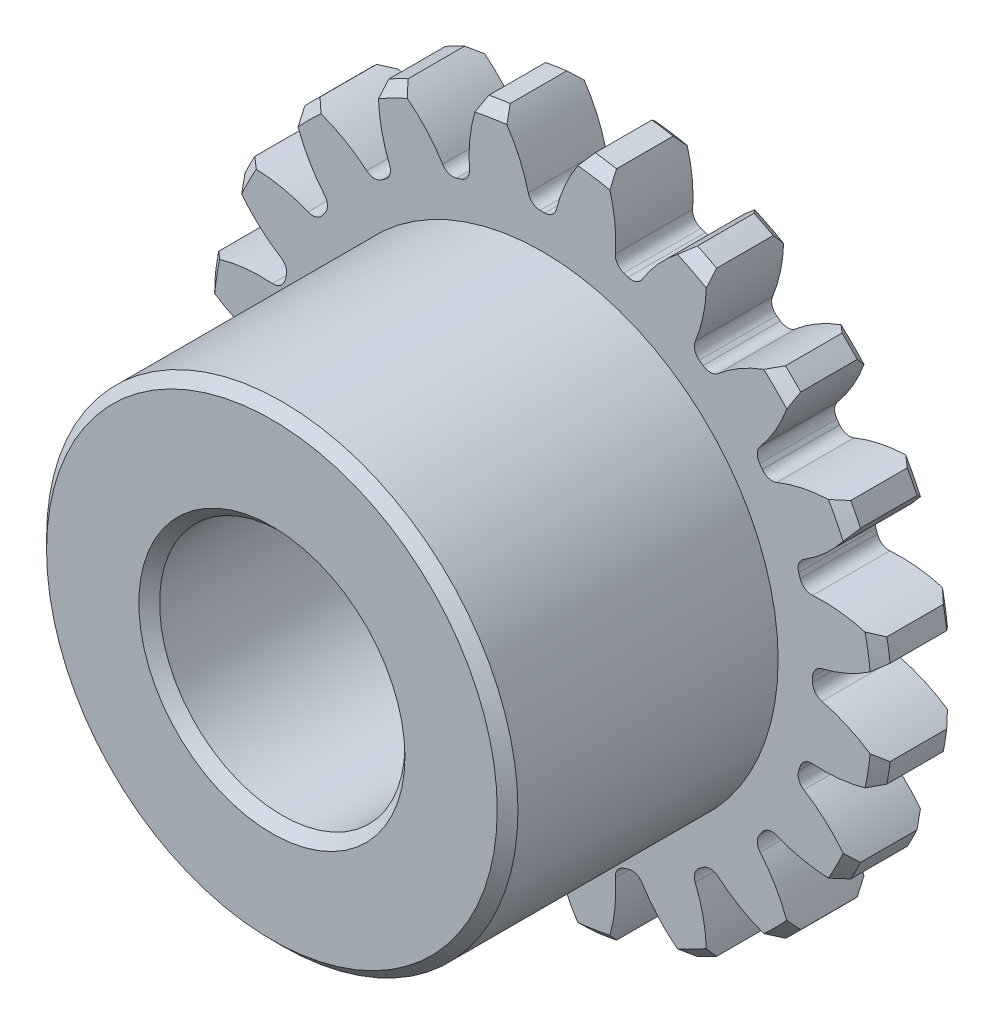
SolidWorks part; units mm, degrees
material "PET"
ref_plane "Front Plane" through (0, 0, 0) normal (0, 0, 1) x (1, 0, 0)
ref_plane "Top Plane" through (0, 0, 0) normal (0, 1, 0) x (1, 0, 0)
ref_plane "Right Plane" through (0, 0, 0) normal (1, 0, 0) x (0, 0, -1)
sketch "Sketch1" plane through (0, 0, 0) normal (0, 0, 1) x (1, 0, 0)
  line L0 (0, 0) -> (0, 8) construction
  line L1 (-2.5712, 8.9358) -> (2.5712, 7.0642) construction
  circle A0 centre (0, 0) radius 7 construction
  circle A1 centre (0, 0) radius 8.8 construction
  circle A2 centre (0, 0) radius 8 construction
  circle A3 centre (0, 0) radius 7.5175 construction
  circle A4 centre (0, 0) radius 6.1 construction
  circle A5 centre (0, 0) radius 3.175 construction
  point P8 (0.4, 0)
  point P13 (10, 0)
  dimension "OD" = 17.6
  dimension "Root Diameter" = 14
  dimension "Gear Pitch Diameter" = 16
  dimension "Base Diameter" = 15.0351
  dimension "Hub Diameter" = 12.2
  dimension "For Shaft Diameter" = 6.35
  dimension "Pressure Angle" = 20
  dimension "Number of Teeth" = 20
  dimension "Module" = 0.8
sketch "Sketch2" plane through (0, 0, 0) normal (1, 0, 0) x (0, 0, -1)
  line L0 (-7, 0) -> (2, 0) construction
  line L1 (2, 8.8) -> (2, -8.8) construction
  line L2 (0, -6.1) -> (-7, -6.1) construction
  line L3 (-7, 8.8) -> (2, 8.8) construction
  line L8 (-7, -6.1) -> (-7, 6.1) construction
  point P4 (0, 8.8)
  point P5 (-3.5, 0)
  dimension "Overall Width" = 9
  dimension "Hub Width" = 7
  dimension "Approx Set Screw Positon" = 3.5
  dimension "Face Width" = 2
sketch "Sketch3" plane through (0, 0, 0) normal (0, 0, 1) x (1, 0, 0)
  circle A0 centre (0, 0) radius 8.8
  circle A1 centre (0, 0) radius 8.8 construction
extrude "Boss-Extrude1" add sketch "Sketch3" against normal up to vertex (2 mm away) and the other way up to vertex (7 mm away) up to point (0, 0, -2) other way up to point (0, 0, 7)
sketch "Sketch5" plane through (0, 0, 0) normal (1, 0, 0) x (0, 0, -1)
  line L1 (0, 6.1) -> (-7, 6.1)
  line L2 (0, 6.1) -> (0, 8.8)
  line L3 (0, 8.8) -> (-7, 8.8)
  line L4 (-7, 6.1) -> (-7, 8.8)
  line L5 (-7, 0) -> (2, 0)
  line L6 (-7, 0) -> (-7, 3.175)
  line L7 (-7, 3.175) -> (2, 3.175)
  line L8 (2, 0) -> (2, 3.175)
  point P5 (0, 6.1)
  point P12 (0, 3.175)
revolve "Cut-Revolve1" cut sketch "Sketch5" angle 360 about L0
sketch "Sketch6" plane through (0, 0, -2) normal (0, 0, 1) x (1, 0, 0)
  line L1 (-6.1, -0.4064) -> (6.1, -0.4064)
  line L2 (-6.1, -0.4064) -> (-6.1, 0.4064)
  line L3 (-6.1, 0.4064) -> (6.1, 0.4064)
  line L4 (6.1, -0.4064) -> (6.1, 0.4064)
  line L5 (0, 0.4064) -> (0, -0.4064) construction
  line L6 (-6.1, 0) -> (6.1, 0) construction
  circle A1 centre (0, 0) radius 6.1 construction
  point P0 (0, 0)
  dimension "D1" = 0.8128
extrude "Cut-Extrude2" cut sketch "Sketch6" along normal blind 1
chamfer "Chamfer1" distance 0.2684 angle 45 6 edges at (8.8, 0, 0) (8.8, 0, -2) (3.175, 0, 7) (6.1, 0, 7) (0, 3.175, -2) (0, -3.175, -2)
sketch "Sketch4" plane through (0, 0, 0) normal (0, 0, 1) x (1, 0, 0)
  line L0 (6.9929, 0.3142) -> (6.9929, -0.3142)
  arc A3 (8.7308, 1.1015) -> (8.7308, -1.1015) centre (0, 0) cw
  circle A4 centre (0, 0) radius 8.8 construction
  arc A5 (6.9929, 0.3142) -> (8.7308, 1.1015) centre (6.2993, 4.157) ccw
  circle A8 centre (0, 0) radius 7 construction
  arc A9 (6.9929, -0.3142) -> (8.7308, -1.1015) centre (6.2993, -4.157) cw
  spline S0 degree 4 poles (7.5023, 0.4781) (7.5044, 0.4782) (7.5101, 0.4787) (7.521, 0.4801) (7.5386, 0.4827) (7.561, 0.4866) (7.5899, 0.4926) (7.6238, 0.5005) (7.6609, 0.5103) (7.7011, 0.5221) (7.741, 0.5348) (7.7807, 0.5484) (7.82, 0.5628) (7.8674, 0.5811) (7.9241, 0.6045) (7.9898, 0.6338) (8.0638, 0.6693) (8.1385, 0.7079) (8.2116, 0.7478) (8.2847, 0.7905) (8.355, 0.8334) (8.4273, 0.8803) (8.4937, 0.9248) (8.5672, 0.9771) (8.6263, 1.0201) (8.7033, 1.0795) (8.7486, 1.1154) (8.8011, 1.1583) (8.8243, 1.1779) (8.8386, 1.1899) knots 0 0 0 0 0 0.005377 0.015084 0.028532 0.04661 0.064855 0.092111 0.119476 0.146842 0.174209 0.201575 0.228941 0.256307 0.307035 0.361767 0.4165 0.471232 0.525964 0.580697 0.635429 0.690161 0.744894 0.799626 0.854358 0.909091 0.954545 1 1 1 1 1 construction
  spline S1 degree 4 poles (7.5023, 0.4781) (7.5044, 0.4782) (7.5101, 0.4787) (7.521, 0.4801) (7.5386, 0.4827) (7.561, 0.4866) (7.5899, 0.4926) (7.6238, 0.5005) (7.6609, 0.5103) (7.7011, 0.5221) (7.741, 0.5348) (7.7807, 0.5484) (7.82, 0.5628) (7.8674, 0.5811) (7.9241, 0.6045) (7.9898, 0.6338) (8.0638, 0.6693) (8.1385, 0.7079) (8.2116, 0.7478) (8.2847, 0.7905) (8.355, 0.8334) (8.4273, 0.8803) (8.4937, 0.9248) (8.5672, 0.9771) (8.6263, 1.0201) (8.6866, 1.0666) (8.7159, 1.0896) (8.7308, 1.1015) knots 0 0 0 0 0 0.005377 0.015084 0.028532 0.04661 0.064855 0.092111 0.119476 0.146842 0.174209 0.201575 0.228941 0.256307 0.307035 0.361767 0.4165 0.471232 0.525964 0.580697 0.635429 0.690161 0.744894 0.799626 0.854358 0.909091 0.909091 0.909091 0.909091 0.909091 construction
  spline S2 degree 4 poles (7.5023, -0.4781) (7.5044, -0.4782) (7.5101, -0.4787) (7.521, -0.4801) (7.5386, -0.4827) (7.561, -0.4866) (7.5899, -0.4926) (7.6238, -0.5005) (7.6609, -0.5103) (7.7011, -0.5221) (7.741, -0.5348) (7.7807, -0.5484) (7.82, -0.5628) (7.8674, -0.5811) (7.9241, -0.6045) (7.9898, -0.6338) (8.0638, -0.6693) (8.1385, -0.7079) (8.2116, -0.7478) (8.2847, -0.7905) (8.355, -0.8334) (8.4273, -0.8803) (8.4937, -0.9248) (8.5672, -0.9771) (8.6263, -1.0201) (8.7033, -1.0795) (8.7486, -1.1154) (8.8011, -1.1583) (8.8243, -1.1779) (8.8386, -1.1899) knots 0 0 0 0 0 0.005377 0.015084 0.028532 0.04661 0.064855 0.092111 0.119476 0.146842 0.174209 0.201575 0.228941 0.256307 0.307035 0.361767 0.4165 0.471232 0.525964 0.580697 0.635429 0.690161 0.744894 0.799626 0.854358 0.909091 0.954545 1 1 1 1 1 construction
  spline S3 degree 4 poles (7.5023, -0.4781) (7.5044, -0.4782) (7.5101, -0.4787) (7.521, -0.4801) (7.5386, -0.4827) (7.561, -0.4866) (7.5899, -0.4926) (7.6238, -0.5005) (7.6609, -0.5103) (7.7011, -0.5221) (7.741, -0.5348) (7.7807, -0.5484) (7.82, -0.5628) (7.8674, -0.5811) (7.9241, -0.6045) (7.9898, -0.6338) (8.0638, -0.6693) (8.1385, -0.7079) (8.2116, -0.7478) (8.2847, -0.7905) (8.355, -0.8334) (8.4273, -0.8803) (8.4937, -0.9248) (8.5672, -0.9771) (8.6263, -1.0201) (8.6866, -1.0666) (8.7159, -1.0896) (8.7308, -1.1015) knots 0 0 0 0 0 0.005377 0.015084 0.028532 0.04661 0.064855 0.092111 0.119476 0.146842 0.174209 0.201575 0.228941 0.256307 0.307035 0.361767 0.4165 0.471232 0.525964 0.580697 0.635429 0.690161 0.744894 0.799626 0.854358 0.909091 0.909091 0.909091 0.909091 0.909091 construction
  dimension "D1" = 0.6283
extrude "Cut-Extrude1" cut sketch "Sketch4" against normal through all both and the other way through all
fillet "Fillet1" radius 0.3142 2 edges at (6.9929, 0.3142, -1) (6.9929, -0.3142, -1)
pattern_circular "CirPattern1" count 20 over 360 about axis through (0, 0, 7) along (0, 0, -1) of "Cut-Extrude1", "Fillet1"
fillet "Fillet2" 2 edges at (6.1, -0.4064, -1.5) (6.1, 0.4064, -1.5) type full round first side face at (4.4105, -0.4064, -1.5732) second side face at (4.3564, 0.4064, -1.5195) middle face at (6.1, 0, -1.5)
fillet "Fillet3" 2 edges at (-6.1, 0.4064, -1.5) (-6.1, -0.4064, -1.5) type full round first side face at (-4.4105, 0.4064, -1.5732) second side face at (-4.3564, -0.4064, -1.5195) middle face at (-6.1, 0, -1.5)
equation "\"Number of Teeth\"= 20"
equation "\"Module\"= 0.8"
equation "\"Diametral Pitch\"= 1 / \"Module\""
equation "\"Dedendum\"= 1.25 / \"Diametral Pitch\""
equation "\"Pitch Diameter\"= \"Module\" * \"Number of Teeth\""
equation "\"Root Diameter\"= \"Pitch Diameter\" - ( 2 * \"Dedendum\" )"
equation "\"Root Diameter@Sketch1\"=\"Root Diameter\""
equation "\"OD@Sketch1\" = \"Outside Diameter\""
equation "\"D1@CirPattern1\"=\"Number of Teeth\""
equation "\"Pressure Angle\"=20"
equation "\"Base Diameter\"= \"Pitch Diameter\" * cos ( \"Pressure Angle\" )"
equation "\"Outside Diameter\"= ( \"Number of Teeth\" + 2 ) / \"Diametral Pitch\""
equation "\"Pitch Angle\"= 360deg / \"Number of Teeth\""
equation "\"Alpha\"= sqr ( \"Pitch Diameter\" ^ 2 - \"Base Diameter\" ^ 2 ) / \"Base Diameter\" * 180 / PI - \"Pressure Angle\""
equation "\"Beta\"= ( \"Pitch Angle\" / 4 - \"Alpha\" )"
equation "\"Phi\"= sqr ( ( \"Outside Diameter\" / 2 ) ^ 2 - ( \"Base Diameter\" / 2 ) ^ 2 ) / ( \"Base Diameter\" / 2 )"
equation "\"Addendum\"= 1 / \"Diametral Pitch\""
equation "\"WorkingDepth\"= 2 / \"Diametral Pitch\""
equation "\"WholeDepth\"= 2.25 / \"Diametral Pitch\""
equation "\"Clearance\"= 0.25 / \"Diametral Pitch\""
equation "\"ToothThickness\"= ( pi * 2 ) / \"Diametral Pitch\""
equation "\"CircularPitch\"= pi / \"Diametral Pitch\""
equation "\"Number of Teeth@Sketch1\"=\"Number of Teeth\""
equation "\"Module@Sketch1\"=\"Module\""
equation "\"Pressure Angle@Sketch1\"=\"Pressure Angle\""
equation "\"Gear Pitch Diameter@Sketch1\"=\"Pitch Diameter\""
equation "\"Base Diameter@Sketch1\"=\"Base Diameter\""
equation "\"Fillet\"= \"Clearance\" * cos ( \"Pressure Angle\" ) * tan ( ( 90 + \"Pressure Angle\" ) / 2 )"
equation "\"Approx Set Screw Positon@Sketch2\" = \"Hub Width@Sketch2\" / 2"
equation "\"D2\"= \"Fillet\" * 2"
equation "\"D1@Chamfer1\"=\"Fillet\""
equation "\"D1@Sketch4\"=\"CircularPitch\"*0.25"
equation "\"D1@Fillet1\"=\"CircularPitch\"*0.125"
